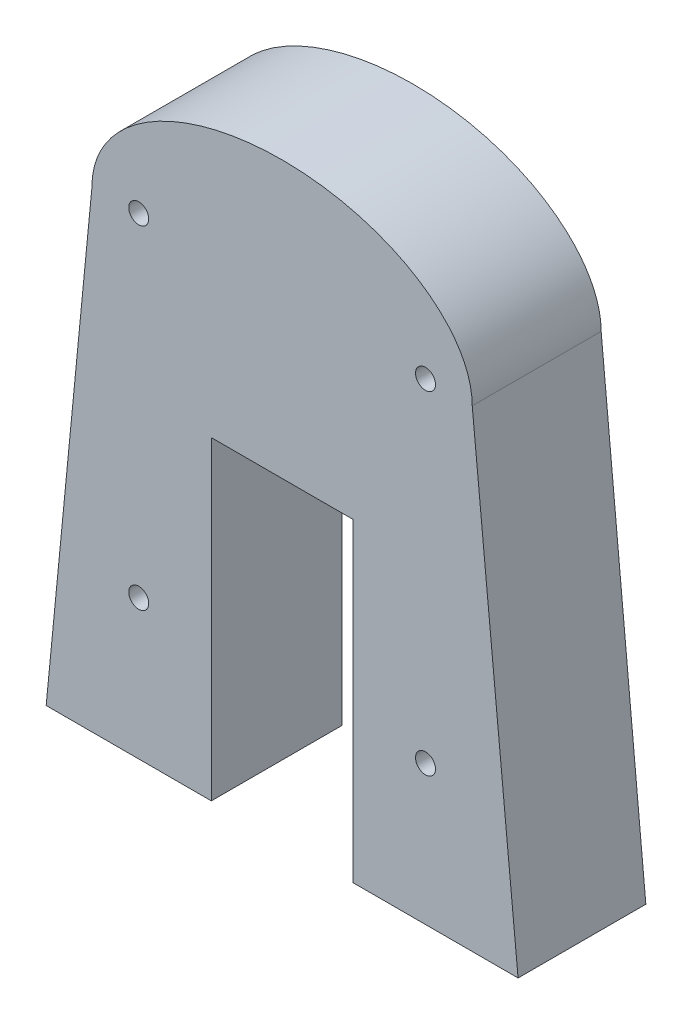
SolidWorks part; units mm, degrees
ref_plane "Front Plane" through (0, 0, 0) normal (0, 0, 1) x (1, 0, 0)
ref_plane "Top Plane" through (0, 0, 0) normal (0, 1, 0) x (1, 0, 0)
ref_plane "Right Plane" through (0, 0, 0) normal (1, 0, 0) x (0, 0, -1)
sketch "Sketch2" plane through (0, 0, 0) normal (0, 0, 1) x (1, 0, 0)
  line L0 (30, 2) -> (30, 24) construction
  line L1 (28, 26) -> (24.5, 26) construction
  line L2 (24.5, 26) -> (24.5, 55.5) construction
  line L3 (24, 56) -> (22.4, 56) construction
  line L4 (21.9, 55.5) -> (21.9, 26) construction
  line L5 (21.9, 26) -> (8.1, 26) construction
  line L6 (8.1, 26) -> (8.1, 55.5) construction
  line L7 (7.6, 56) -> (6, 56) construction
  line L8 (5.5, 55.5) -> (5.5, 26) construction
  line L9 (5.5, 26) -> (2, 26) construction
  line L10 (0, 24) -> (0, 2) construction
  line L11 (2, 0) -> (11.4, 0) construction
  line L12 (11.4, 0) -> (11.4, 1.2) construction
  line L13 (11.4, 1.2) -> (18.6, 1.2) construction
  line L14 (18.6, 1.2) -> (18.6, 0) construction
  line L15 (18.6, 0) -> (28, 0) construction
  line L16 (22.4, 54) -> (22.4, 52.1) construction
  line L17 (24, 52.1) -> (24, 54) construction
  line L18 (7.6, 51.45) -> (7.6, 54.65) construction
  line L19 (7.6, 54.65) -> (6, 54.65) construction
  line L20 (6, 54.65) -> (6, 51.45) construction
  line L21 (6, 51.45) -> (7.6, 51.45) construction
  line L22 (24, 56.1) -> (22.4, 56.1)
  line L23 (21.8, 55.5) -> (21.8, 26.1)
  line L24 (21.8, 26.1) -> (8.2, 26.1)
  line L25 (8.2, 26.1) -> (8.2, 55.5)
  line L26 (7.6, 56.1) -> (6, 56.1)
  line L27 (5.4, 55.5) -> (5.4, 26.1)
  line L28 (5.4, 26.1) -> (2, 26.1)
  line L29 (-0.1, 24) -> (-0.1, 2)
  line L30 (2, -0.1) -> (11.5, -0.1)
  line L31 (11.5, -0.1) -> (11.5, 1.1)
  line L32 (11.5, 1.1) -> (18.5, 1.1)
  line L33 (18.5, 1.1) -> (18.5, -0.1)
  line L34 (18.5, -0.1) -> (28, -0.1)
  line L35 (30.1, 2) -> (30.1, 24)
  line L36 (28, 26.1) -> (24.6, 26.1)
  line L37 (24.6, 26.1) -> (24.6, 55.5)
  arc A0 (30, 24) -> (28, 26) centre (28, 24) ccw construction
  arc A1 (24.5, 55.5) -> (24, 56) centre (24, 55.5) ccw construction
  arc A2 (22.4, 56) -> (21.9, 55.5) centre (22.4, 55.5) ccw construction
  arc A3 (28, 0) -> (30, 2) centre (28, 2) ccw construction
  arc A4 (8.1, 55.5) -> (7.6, 56) centre (7.6, 55.5) ccw construction
  arc A5 (6, 56) -> (5.5, 55.5) centre (6, 55.5) ccw construction
  arc A6 (2, 26) -> (0, 24) centre (2, 24) ccw construction
  arc A7 (0, 2) -> (2, 0) centre (2, 2) ccw construction
  circle A8 centre (4, 22) radius 1.55
  circle A9 centre (26, 22) radius 1.55
  circle A10 centre (4, 4) radius 1.55 construction
  circle A11 centre (26, 4) radius 1.55 construction
  circle A12 centre (10, 3.81) radius 0.6 construction
  circle A13 centre (10, 1.31) radius 0.6 construction
  circle A14 centre (20, 1.31) radius 0.6 construction
  circle A15 centre (20, 3.81) radius 0.6 construction
  circle A16 centre (15, 8.81) radius 0.6 construction
  arc A17 (23.6, 51.45) -> (22.8, 51.45) centre (23.2, 51.4242) ccw construction
  arc A18 (23.5747, 51.4484) -> (23.6253, 51.4516) centre (23.6, 51.45) ccw construction
  arc A19 (22.7747, 51.4516) -> (22.8253, 51.4484) centre (22.8, 51.45) ccw construction
  arc A20 (22.3746, 52.1) -> (22.4254, 52.1) centre (22.4, 52.1) ccw construction
  arc A21 (22.4254, 54) -> (22.3746, 54) centre (22.4, 54) ccw construction
  arc A22 (24.0254, 54) -> (23.9746, 54) centre (24, 54) ccw construction
  arc A23 (23.9746, 52.1) -> (24.0254, 52.1) centre (24, 52.1) ccw construction
  circle A24 centre (22.65, 51.625) radius 0.1 construction
  arc A25 (7.6318, 54.65) -> (7.5683, 54.65) centre (7.6001, 54.65) ccw construction
  arc A26 (7.5683, 51.45) -> (7.6318, 51.45) centre (7.6001, 51.45) ccw construction
  arc A27 (6, 54.6818) -> (6, 54.6183) centre (6, 54.6501) ccw construction
  arc A28 (7.6, 54.6183) -> (7.6, 54.6818) centre (7.6, 54.6501) ccw construction
  arc A29 (5.9683, 51.45) -> (6.0317, 51.45) centre (6, 51.45) ccw construction
  arc A30 (6.0317, 54.65) -> (5.9683, 54.65) centre (6, 54.65) ccw construction
  arc A31 (7.6, 51.4183) -> (7.6, 51.4818) centre (7.6, 51.45) ccw construction
  arc A32 (6, 51.4818) -> (6, 51.4183) centre (6, 51.45) ccw construction
  circle A33 centre (7.15, 50.05) radius 0.15 construction
  circle A34 centre (26, 22) radius 1.5 construction
  circle A35 centre (4, 22) radius 1.5 construction
  arc A36 (22.4, 56.1) -> (21.8, 55.5) centre (22.4, 55.5) ccw
  arc A37 (8.2, 55.5) -> (7.6, 56.1) centre (7.6, 55.5) ccw
  arc A38 (6, 56.1) -> (5.4, 55.5) centre (6, 55.5) ccw
  arc A39 (2, 26.1) -> (-0.1, 24) centre (2, 24) ccw
  arc A40 (-0.1, 2) -> (2, -0.1) centre (2, 2) ccw
  arc A41 (28, -0.1) -> (30.1, 2) centre (28, 2) ccw
  arc A42 (30.1, 24) -> (28, 26.1) centre (28, 24) ccw
  arc A43 (24.6, 55.5) -> (24, 56.1) centre (24, 55.5) ccw
  dimension "D1" = 3
  dimension "D2" = 0.1
sketch "Sketch3" plane through (0, 0, 0) normal (0, 0, 1) x (1, 0, 0)
  line L0 (15, 26) -> (15, 53.05) construction
  line L1 (21.9, 26) -> (8.1, 26) construction
  line L2 (6, 53.05) -> (15, 53.05) construction
  line L3 (6, 54.65) -> (6, 51.45) construction
  line L4 (0.4984, 53.05) -> (29.5016, 53.05) construction
  line L5 (2.5, 53.05) -> (27.5, 53.05) construction
  line L7 (24.5, 26) -> (24.5, 55.5) construction
  line L9 (-3, 17) -> (9.6, 17)
  line L10 (9.6, 17) -> (9.6, 41)
  line L11 (9.6, 41) -> (20.4, 41)
  line L12 (20.4, 41) -> (20.4, 17)
  line L13 (20.4, 17) -> (33, 17)
  line L14 (33, 17) -> (29.5016, 53.05)
  line L15 (-3, 17) -> (0.4984, 53.05)
  line L16 (8.1, 26) -> (8.1, 55.5) construction
  line L17 (0, 24) -> (0, 2) construction
  circle A0 centre (15, 53.05) radius 6
  arc A1 (0.4984, 53.05) -> (29.5016, 53.05) centre (15, 53.05) cw construction
  circle A2 centre (27.5, 53.05) radius 0.5953 construction
  circle A3 centre (2.5, 53.05) radius 0.5953 construction
  circle A4 centre (4, 22) radius 1.55 construction
  ellipse E0 centre (15, 53.05) end of major axis (0.4984, 53.05) minor radius 9 (29.5016, 53.05) -> (0.4984, 53.05) ccw
  point P6 (0, 0)
  point P20 (0, 0)
  point P23 (15, 41)
  dimension "D1" = 12
  dimension "D2" = 1.1906
  dimension "D5" = 5
  dimension "D3" = 3
  dimension "D4" = 1.5
  dimension "D6" = 3
  dimension "D7" = 15
  dimension "D8" = 2.0016
  dimension "D9" = 9
extrude "Boss-Extrude1" add sketch "Sketch3" along normal blind 10 contours A1 L15 L9 L10 L11 L12 L13 L14 A0 | A0 region at (-0.6768, 34.9693, 0) region at (15, 53.05, 0)
ref_plane "Plane1" through (15, 0, 0) normal (1, 0, 0) x (0, 1, 0)
sketch "Sketch5" plane through (15, 0, 0) normal (1, 0, 0) x (0, 1, 0)
  line L0 (53.05, 5) -> (47.05, 5) construction
  line L3 (47.05, 5) -> (47.05, 0) construction
  line L4 (47.05, 10) -> (47.05, 0)
  line L9 (53.05, 0) -> (53.05, 4.2876) construction
  line L10 (47.05, 5) -> (45.55, 5) construction
  arc A0 (47.05, 0) -> (47.05, 10) centre (54.6333, 5) cw
  dimension "D1" = 5
  dimension "D2" = 1.5
sketch "Sketch6" plane through (0, 0, 0) normal (0, 0, -1) x (-1, 0, 0)
  line L0 (-27.5308, 39.1414) -> (-2.1308, 39.1414)
  line L1 (-5.4, 50.6) -> (-24.6, 50.6)
  line L2 (-5.4, 50.6) -> (-5.4, 55.5)
  line L3 (-5.4, 55.5) -> (-24.6, 55.5)
  line L4 (-24.6, 50.6) -> (-24.6, 55.5)
  line L5 (-5.4, 50.6) -> (-24.6, 55.5) construction
  line L6 (-5.4, 55.5) -> (-24.6, 50.6) construction
  line L7 (-2.1308, 39.1414) -> (-2.1308, 64.5414)
  line L8 (-2.1308, 64.5414) -> (-27.5308, 64.5414)
  line L9 (-27.5308, 64.5414) -> (-27.5308, 39.1414)
  line L10 (-21.5566, 45.1156) -> (-8.1051, 45.1156)
  line L11 (-8.1051, 45.1156) -> (-8.1051, 58.5671)
  line L12 (-8.1051, 58.5671) -> (-21.5566, 58.5671)
  line L13 (-21.5566, 58.5671) -> (-21.5566, 45.1156)
  line L32 (-8.1051, 51.8414) -> (-2.1308, 51.8414) construction
  line L33 (-21.5566, 51.8414) -> (-27.5308, 51.8414) construction
  line L34 (-14.8308, 41.7583) -> (-14.8308, 39.1414) construction
  line L35 (-12.2908, 44.2983) -> (-17.3708, 44.2983)
  line L36 (-12.2908, 44.2983) -> (-12.2908, 41.7583)
  line L37 (-12.2908, 41.7583) -> (-17.3708, 41.7583)
  line L38 (-17.3708, 44.2983) -> (-17.3708, 41.7583)
  circle A0 centre (-24.9908, 62.0014) radius 1.5875
  circle A1 centre (-24.9908, 41.6814) radius 1.5875
  circle A2 centre (-4.6708, 41.6814) radius 1.5875
  circle A3 centre (-4.6708, 62.0014) radius 1.5875
  point P0 (-15, 53.05)
  point P28 (-2.5977, -7.62)
  point P29 (18.5404, -12.777)
  point P30 (1.0719, -3.2305)
  point P31 (-27.5308, 39.1414)
  dimension "D2" = 3.175
  dimension "D1" = 25.4
  dimension "D3" = 2.54
  dimension "D4" = 2.54
  dimension "D5" = 2.54
  dimension "D6" = 2.54
  dimension "D7" = 5.08
  dimension "D8" = 2.54
  dimension "D9" = 2.617
sketch "Sketch10" plane through (0, 0, 0) normal (0, 1, 0) x (1, 0, 0)
  line L0 (15, 0) -> (15, -636.6198) construction
  line L1 (15, 0) -> (15, 76.2) construction
  line L2 (15, 76.2) -> (15, 77.7875) construction
  line L3 (20.4, 0) -> (9.6, 0)
  line L4 (15, 77.7875) -> (15, 0) construction
  line L5 (52.3892, 76.8084) -> (15, -636.6198) construction
  line L6 (-22.3892, 76.8084) -> (15, -636.6198) construction
  line L7 (-18.3181, -0.8725) -> (-22.3892, 76.8084)
  line L8 (48.3181, -0.8725) -> (52.3892, 76.8084)
  line L9 (15, -636.6198) -> (2.5319, 77.6787) construction
  line L10 (150.1593, 80.2555) -> (-145.0955, 75.1018)
  arc A0 (52.3892, 76.8084) -> (-22.3892, 76.8084) centre (15, -636.6198) ccw
  arc A1 (48.3181, -0.8725) -> (-18.3181, -0.8725) centre (15, -636.6198) ccw
  point P8 (0, 0)
  point P16 (2.5319, 77.6787)
  point P42 (3.8895, -0.097)
  dimension "D1" = 636.6198
  dimension "D2" = 76.2
  dimension "D3" = 1.5875
  dimension "D4" = 1
  dimension "D5" = 3
extrude "Cut-Extrude-TrackWallCurve" cut sketch "Sketch10" along normal through all contours A1 L8 A0 L7 region at (15, 0, -39.3312)
ref_plane "Plane3" through (3.8895, 0, 0.097) normal (-0.0175, 0, -0.9998) x (-0.9998, 0, 0.0175)
sketch "Sketch11" plane through (3.8895, 0, 0.097) normal (-0.0175, 0, -0.9998) x (-0.9998, 0, 0.0175)
  line L0 (0, 53.05) -> (0, 27.65) construction
  line L1 (0, 27.65) -> (0, 0) construction
  circle A0 centre (0, 53.05) radius 0.762
  circle A1 centre (0, 27.65) radius 0.762
  dimension "D2" = 1.524
  dimension "D1" = 25.4
extrude "Cut-Extrude4" cut sketch "Sketch11" along normal blind 7 and the other way blind 25.4
mirror "Mirror2" about plane through (15, 0, 0) normal (1, 0, 0) of "Cut-Extrude4"
equation "\"D2@Sketch10\"=3in"
equation "\"D3@Sketch10\"=1in/16"
